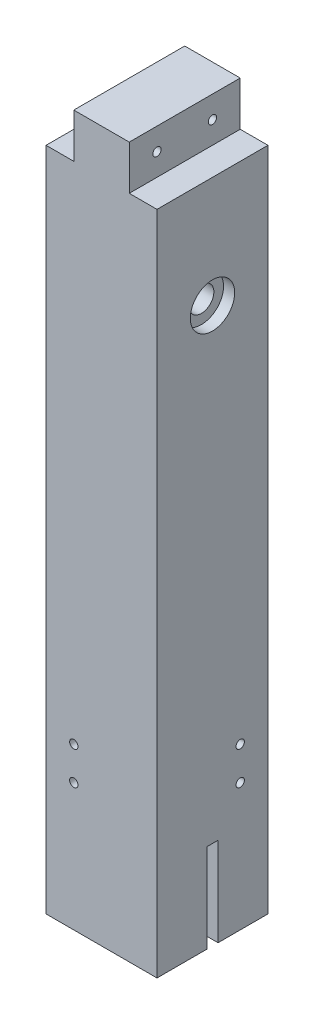
SolidWorks part; units mm, degrees
ref_plane "Front Plane" through (0, 0, 0) normal (0, 0, 1) x (1, 0, 0)
ref_plane "Top Plane" through (0, 0, 0) normal (0, 1, 0) x (1, 0, 0)
ref_plane "Right Plane" through (0, 0, 0) normal (1, 0, 0) x (0, 0, -1)
sketch "Sketch1" plane through (0, 0, 0) normal (0, 0, 1) x (1, 0, 0)
  line L1 (63.5, 381) -> (-63.5, 381)
  line L2 (63.5, 381) -> (63.5, -381)
  line L3 (63.5, -381) -> (-63.5, -381)
  line L4 (-63.5, 381) -> (-63.5, -381)
  line L5 (63.5, 381) -> (-63.5, -381) construction
  line L6 (63.5, -381) -> (-63.5, 381) construction
  line L7 (31.75, 431.8) -> (-31.75, 431.8)
  line L8 (31.75, 431.8) -> (31.75, 330.2)
  line L9 (31.75, 330.2) -> (-31.75, 330.2)
  line L10 (-31.75, 431.8) -> (-31.75, 330.2)
  line L11 (31.75, 431.8) -> (-31.75, 330.2) construction
  line L12 (31.75, 330.2) -> (-31.75, 431.8) construction
  point P0 (0, 0)
  point P6 (0, 381)
  dimension "D1" = 762
  dimension "D2" = 101.6
  dimension "D3" = 63.5
  dimension "D4" = 127
extrude "Boss-Extrude1" add sketch "Sketch1" along normal blind 127 contours L10 L1 L4 L3 L2 L8 L9 | L1 L10 L9 L8 | L7 L10 L1 L8 region at (0, -12.2621, 0) region at (0, 355.6, 0) region at (0, 406.4, 0)
sketch "Sketch2" plane through (63.5, 0, 0) normal (1, 0, 0) x (0, 0, -1)
  line L0 (-63.5, -381) -> (-63.5, 49619) construction
  line L1 (-127, -381) -> (0, -381) construction
  line L2 (-127, 406.4) -> (0, 406.4) construction
  line L3 (-57.15, -482.6) -> (-69.85, -482.6)
  line L4 (-57.15, -482.6) -> (-57.15, -279.4)
  line L5 (-57.15, -279.4) -> (-69.85, -279.4)
  line L6 (-69.85, -482.6) -> (-69.85, -279.4)
  line L7 (-57.15, -482.6) -> (-69.85, -279.4) construction
  line L8 (-57.15, -279.4) -> (-69.85, -482.6) construction
  line L9 (-127, 431.8) -> (-127, 381) construction
  line L10 (0, 431.8) -> (0, 381) construction
  circle A0 centre (-63.5, 254) radius 25.4
  circle A1 centre (-63.5, 254) radius 14.2875
  circle A2 centre (-95.25, 406.4) radius 4.7625
  circle A3 centre (-31.75, 406.4) radius 4.7625
  point P4 (-63.5, -381)
  point P5 (-63.5, -381)
  line M7 (-127, -381) -> (0, -381)
  dimension "D3" = 50.8
  dimension "D4" = 28.575
  dimension "D5" = 635
  dimension "D6" = 9.525
  dimension "D7" = 31.75
  dimension "D8" = 31.75
  dimension "D1" = 203.2
  dimension "D2" = 12.7
extrude "Cut-Extrude1" cut sketch "Sketch2" against normal through all contours A2 | A3 | A1 | L6 L4 L5 M7 region at (63.5, -330.2, 63.5) region at (63.5, 254, 63.5) region at (63.5, 406.4, 95.25) region at (63.5, 406.4, 31.75)
sketch "Sketch3" plane through (0, 0, 0) normal (0, 0, -1) x (-1, 0, 0)
  line L0 (-63.5, 381) -> (-63.5, -381) construction
  line L1 (0, -177.8) -> (-31.75, -177.8)
  line L2 (0, -177.8) -> (0, -254)
  line L3 (0, -254) -> (-31.75, -254)
  line L4 (-31.75, -177.8) -> (-31.75, -254)
  line L5 (0, -177.8) -> (-31.75, -254) construction
  line L6 (0, -254) -> (-31.75, -177.8) construction
  line L7 (-63.5, -381) -> (63.5, -381) construction
  point P0 (-15.875, -215.9)
  dimension "D1" = 76.2
  dimension "D2" = 31.75
  dimension "D3" = 31.75
  dimension "D4" = 127
extrude "Cut-Extrude2" cut sketch "Sketch3" against normal blind 63.5
extrude "Cut-Extrude3" cut sketch "Sketch2<3>" against normal blind 12.7 contours A0 A1 region at (63.5, 254, 88.1816)
sketch "Sketch2<3>" plane through (63.5, 0, 0) normal (1, 0, 0) x (0, 0, -1) same geometry as "Sketch2"
sketch "Sketch4" plane through (63.5, 0, 0) normal (1, 0, 0) x (0, 0, -1)
  line L0 (-31.75, -177.8) -> (-31.75, -254) construction
  line L4 (0, -254) -> (0, -177.8)
  line L5 (-63.5, -254) -> (0, -254)
  line L6 (-63.5, -177.8) -> (-63.5, -254)
  line L7 (0, -177.8) -> (-63.5, -177.8)
  line L8 (0, -254) -> (0, -177.8)
  line L9 (-63.5, -254) -> (0, -254)
  line L10 (-63.5, -177.8) -> (-63.5, -254)
  line L11 (0, -177.8) -> (-63.5, -177.8)
  circle A0 centre (-31.75, -234.95) radius 4.7625
  circle A1 centre (-31.75, -196.85) radius 4.7625
  point P10 (-31.75, -215.9)
  dimension "D2" = 19.05
  dimension "D3" = 19.05
  dimension "D4" = 9.525
  dimension "D5" = 31.75
  dimension "D1" = 0
extrude "Cut-Extrude4" cut sketch "Sketch4" against normal blind 69.85 contours A0 L0 | L0 A0 | A1 L0 | L0 A1 region at (63.5, -196.85, 29.7287) region at (63.5, -196.85, 33.7713) region at (63.5, -234.95, 29.7287) region at (63.5, -234.95, 33.7713)
sketch "Sketch5" plane through (-63.5, 0, 0) normal (-1, 0, 0) x (0, 0, 1)
  line L0 (127, 381) -> (127, -381) construction
  line L1 (95.25, -177.8) -> (63.5, -177.8)
  line L2 (95.25, -177.8) -> (95.25, -254)
  line L3 (95.25, -254) -> (63.5, -254)
  line L4 (63.5, -177.8) -> (63.5, -254)
  line L5 (95.25, -177.8) -> (63.5, -254) construction
  line L6 (95.25, -254) -> (63.5, -177.8) construction
  line L7 (127, -381) -> (69.85, -381) construction
  point P0 (79.375, -215.9)
  dimension "D1" = 76.2
  dimension "D2" = 31.75
  dimension "D3" = 31.75
  dimension "D4" = 127
extrude "Cut-Extrude6" cut sketch "Sketch5" against normal blind 63.246
sketch "Sketch6" plane through (0, 0, 127) normal (0, 0, 1) x (1, 0, 0)
  line L0 (-31.75, -177.8) -> (-31.75, -254) construction
  line L4 (-63.5, -177.8) -> (-63.5, -254)
  line L5 (-0.254, -177.8) -> (-63.5, -177.8)
  line L6 (-0.254, -254) -> (-0.254, -177.8)
  line L7 (-63.5, -254) -> (-0.254, -254)
  line L8 (-63.5, -177.8) -> (-63.5, -254)
  line L9 (-0.254, -177.8) -> (-63.5, -177.8)
  line L10 (-0.254, -254) -> (-0.254, -177.8)
  line L11 (-63.5, -254) -> (-0.254, -254)
  circle A0 centre (-31.75, -234.95) radius 4.7625
  circle A1 centre (-31.75, -196.85) radius 4.7625
  point P10 (-31.75, -215.9)
  dimension "D2" = 9.525
  dimension "D4" = 19.05
  dimension "D3" = 19.05
  dimension "D5" = 31.75
  dimension "D1" = 0
extrude "Cut-Extrude7" cut sketch "Sketch6" against normal blind 69.85 contours A0 L0 | L0 A0 | L0 A1 | A1 L0 region at (-29.7287, -196.85, 127) region at (-33.7713, -196.85, 127) region at (-29.7287, -234.95, 127) region at (-33.7713, -234.95, 127)
